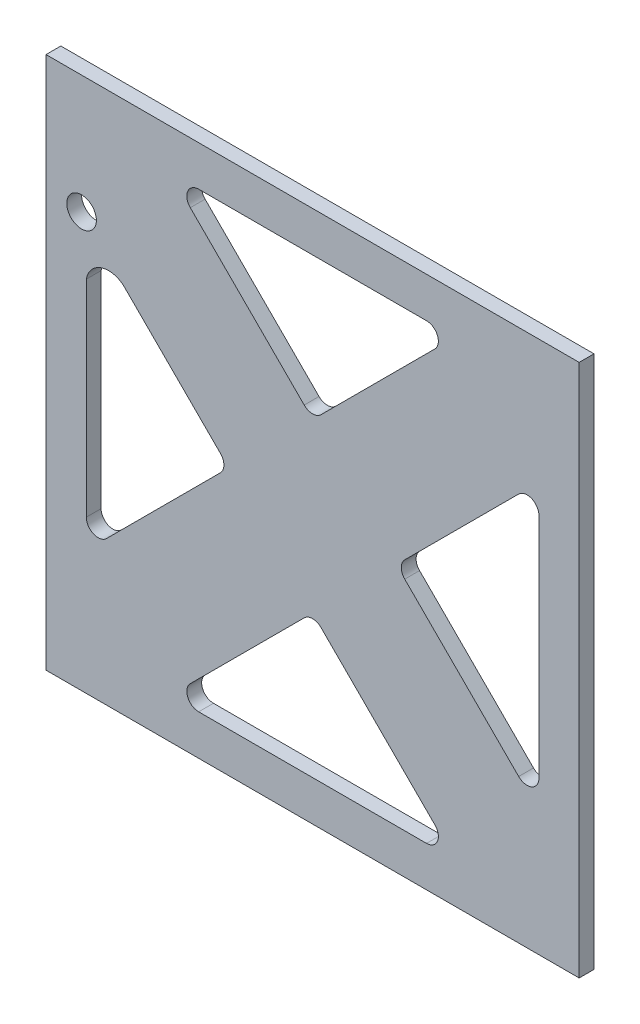
SolidWorks part; units mm, degrees
ref_plane "Front Plane" through (0, 0, 0) normal (0, 0, 1) x (1, 0, 0)
ref_plane "Top Plane" through (0, 0, 0) normal (0, 1, 0) x (1, 0, 0)
ref_plane "Right Plane" through (0, 0, 0) normal (1, 0, 0) x (0, 0, -1)
sketch "Sketch1" plane through (0, 0, 0) normal (0, 0, 1) x (1, 0, 0)
  line L5 (-57.15, -57.15) -> (57.15, -57.15)
  line L6 (-57.15, -57.15) -> (-57.15, 57.15)
  line L7 (-57.15, 57.15) -> (57.15, 57.15)
  line L13 (57.15, -57.15) -> (57.15, 57.15)
  line L23 (-57.15, -57.15) -> (-49.7355, -49.7355) construction
  line L25 (-24.4252, -48.5178) -> (24.4252, -48.5178)
  line L41 (49.7355, 49.7355) -> (57.15, 57.15) construction
  line L44 (-1.7961, -19.7566) -> (-26.2212, -44.1818)
  line L45 (-57.15, 57.15) -> (57.15, -57.15) construction
  line L46 (1.7961, -19.7566) -> (26.2212, -44.1818)
  line L48 (0, -48.5178) -> (0, -34.0814) construction
  line L49 (-48.5178, 19.7566) -> (-48.5178, -24.4252)
  line L50 (-19.7566, 1.7961) -> (-40.426, 22.4655)
  line L51 (-19.7566, -1.7961) -> (-44.1818, -26.2212)
  line L52 (-48.5178, 0) -> (-34.0814, 0) construction
  line L53 (24.4252, 48.5178) -> (-24.4252, 48.5178)
  line L54 (1.7961, 19.7566) -> (26.2212, 44.1818)
  line L55 (-1.7961, 19.7566) -> (-26.2212, 44.1818)
  line L56 (0, 48.5178) -> (0, 34.0814) construction
  line L57 (48.5178, -24.4252) -> (48.5178, 24.4252)
  line L58 (19.7566, -1.7961) -> (44.1818, -26.2212)
  line L59 (19.7566, 1.7961) -> (44.1818, 26.2212)
  line L60 (48.5178, 0) -> (34.0814, 0) construction
  circle A27 centre (-49.53, 31.75) radius 3.175
  arc A34 (24.4252, -48.5178) -> (26.2212, -44.1818) centre (24.4252, -45.9778) ccw
  arc A35 (-26.2212, -44.1818) -> (-24.4252, -48.5178) centre (-24.4252, -45.9778) ccw
  arc A36 (-1.7961, -19.7566) -> (1.7961, -19.7566) centre (0, -21.5526) cw
  arc A40 (-48.5178, -24.4252) -> (-44.1818, -26.2212) centre (-45.9778, -24.4252) ccw
  arc A42 (-19.7566, 1.7961) -> (-19.7566, -1.7961) centre (-21.5526, 0) cw
  arc A43 (-24.4252, 48.5178) -> (-26.2212, 44.1818) centre (-24.4252, 45.9778) ccw
  arc A44 (26.2212, 44.1818) -> (24.4252, 48.5178) centre (24.4252, 45.9778) ccw
  arc A45 (1.7961, 19.7566) -> (-1.7961, 19.7566) centre (0, 21.5526) cw
  arc A46 (48.5178, 24.4252) -> (44.1818, 26.2212) centre (45.9778, 24.4252) ccw
  arc A47 (44.1818, -26.2212) -> (48.5178, -24.4252) centre (45.9778, -24.4252) ccw
  arc A48 (19.7566, -1.7961) -> (19.7566, 1.7961) centre (21.5526, 0) cw
  arc A49 (-44.1818, 26.2212) -> (-48.5178, 24.4252) centre (-45.9778, 24.4252) ccw [skipped]
  arc A50 (-40.426, 22.4655) -> (-48.5178, 19.7566) centre (-43.7232, 18.8746) ccw
  point P0 (0, 0)
  point P8 (0, 0)
  point P9 (0, 0)
  point P18 (0, 0)
  point P46 (0, -17.9605)
  point P60 (0, 0)
  dimension "D3" = 25.4
  dimension "D4" = 6.35
  dimension "D6" = 12.7
  dimension "D7" = 8.6322
  dimension "D8" = 4
  dimension "D5" = 2.54
  dimension "D1" = 7.62
  dimension "D2" = 114.3
extrude "Boss-Extrude2" add sketch "Sketch1" along normal mid plane 3.175
sketch "Sketch2" plane through (0, 0, -1.5875) normal (0, 0, -1) x (-1, 0, 0)
  line L0 (57.15, 44.45) -> (63.5, 44.45)
  line L1 (63.5, 44.45) -> (63.5, 19.05)
  line L2 (63.5, 19.05) -> (57.15, 19.05)
  line L3 (57.15, 57.15) -> (57.15, -57.15) construction
  line L4 (57.15, 19.05) -> (57.15, 44.45)
  line L5 (-57.15, 57.15) -> (57.15, 57.15) construction
  dimension "D1" = 12.7
  dimension "D2" = 6.35
  dimension "D3" = 25.4
extrude "Boss-Extrude3" [suppressed] add sketch "Sketch2" against normal blind 3.175
